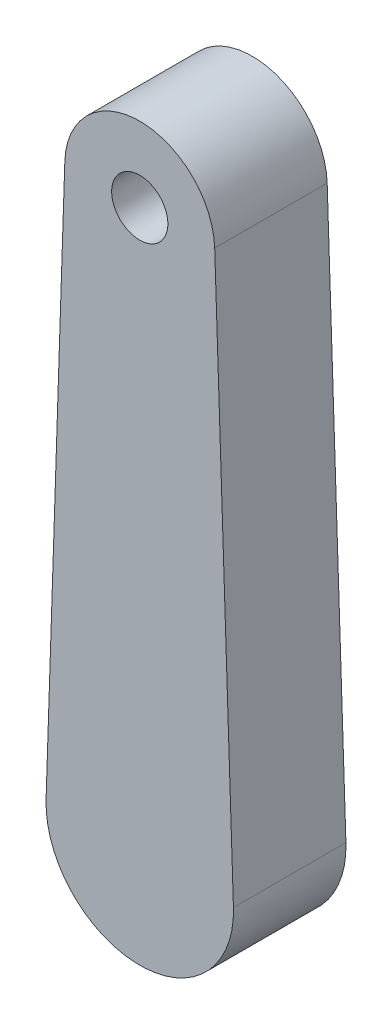
SolidWorks part; units mm, degrees
material "ABS"
ref_plane "Front Plane" through (0, 0, 0) normal (0, 0, 1) x (1, 0, 0)
ref_plane "Top Plane" through (0, 0, 0) normal (0, 1, 0) x (1, 0, 0)
ref_plane "Right Plane" through (0, 0, 0) normal (1, 0, 0) x (0, 0, -1)
sketch "Sketch1" plane through (0, 0, 0) normal (0, 0, 1) x (1, 0, 0)
  line L0 (-1.9912, 16.1875) -> (-3.4846, 0.3281)
  line L1 (3.4846, 0.3281) -> (1.9912, 16.1875)
  arc A0 (-3.4846, 0.3281) -> (3.4846, 0.3281) centre (0, 0) ccw
  arc A1 (1.9912, 16.1875) -> (-1.9912, 16.1875) centre (0, 16) ccw
  dimension "D1" = 7
  dimension "D3" = 4
  dimension "D2" = 16
sketch "Sketch2" plane through (0, 0, 0) normal (0, 0, 1) x (1, 0, 0)
  line L0 (0, 0) -> (0, 30) construction
  line L4 (-4.9972, 0.1667) -> (-3.9978, 30.1333)
  line L5 (4.9972, 0.1667) -> (3.9978, 30.1333)
  line L6 (-4.9747, 51.9884) -> (2.411, 22.9117) construction
  arc A3 (3.9978, 30.1333) -> (-3.9978, 30.1333) centre (0, 30) ccw
  arc A4 (-4.9972, 0.1667) -> (4.9972, 0.1667) centre (0, 0) ccw
  circle A5 centre (0, 30) radius 1.5
  dimension "D1" = 3
  dimension "D2" = 4
  dimension "D3" = 5
extrude "Boss-Extrude1" add sketch "Sketch2" along normal mid plane 6
extrude "Cut-Extrude1" cut sketch "Sketch1" against normal through all and the other way blind 1
ref_axis "Axis1" through (0, 30, 3) along (0, 0, -1)
ref_axis "Axis2" through (0, 0, 1) along (0, 0, -1)
